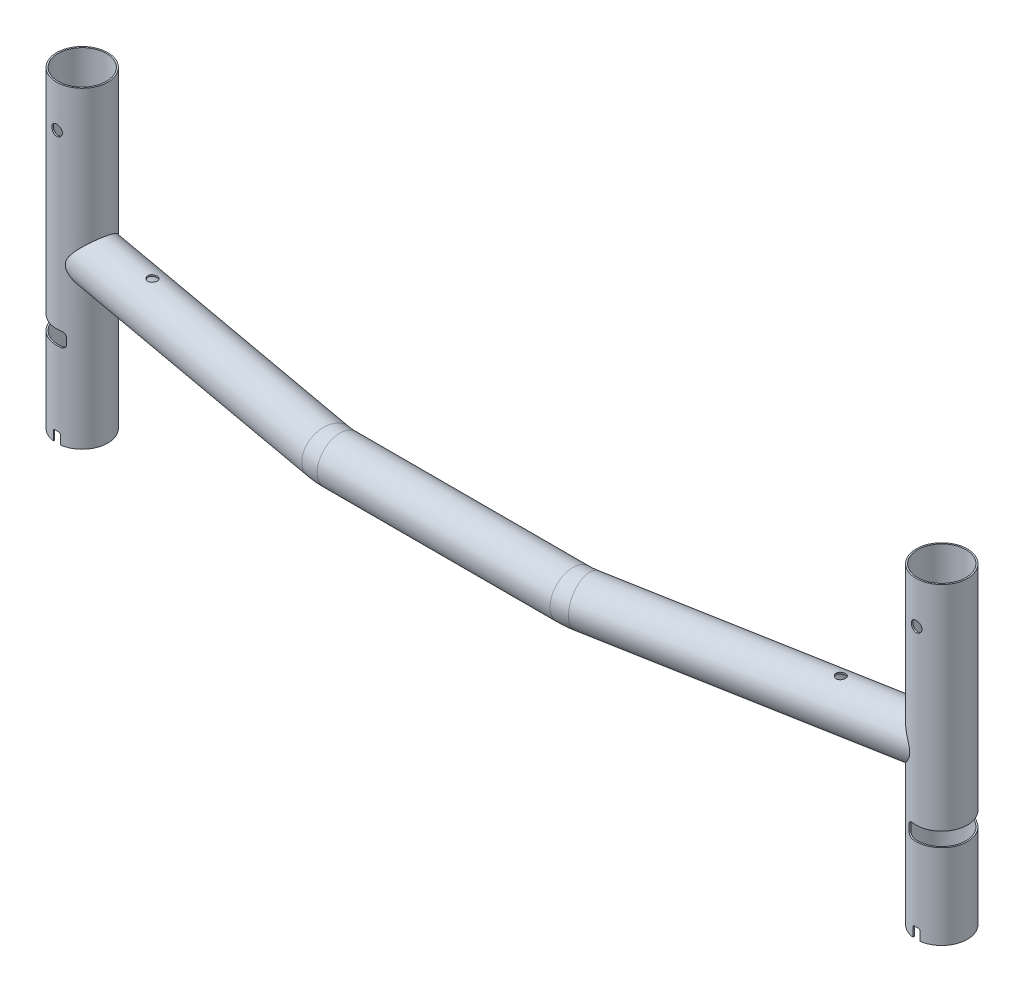
SolidWorks part; units mm, degrees
ref_plane "Front Plane" through (0, 0, 0) normal (0, 0, 1) x (1, 0, 0)
ref_plane "Top Plane" through (0, 0, 0) normal (0, 1, 0) x (1, 0, 0)
ref_plane "Right Plane" through (0, 0, 0) normal (1, 0, 0) x (0, 0, -1)
sketch "Sketch1" plane through (0, 0, 0) normal (0, 1, 0) x (1, 0, 0)
  line L0 (0, 0) -> (0, 107.988) construction
  line L1 (-65, 0) -> (65, 0)
  line L2 (72.1386, 0.6421) -> (234, 30)
  line L3 (-72.1386, 0.6421) -> (-234, 30)
  arc A0 (72.1386, 0.6421) -> (65, 0) centre (65, 40) cw
  arc A1 (-72.1386, 0.6421) -> (-65, 0) centre (-65, 40) ccw
  dimension "D2" = 40
  dimension "D1" = 234
  dimension "D3" = 65
  dimension "D4" = 30
ref_plane "Plane1" through (234, 0, -30) normal (0.9839, 0, -0.1785) x (-0.1785, 0, -0.9839)
sketch "Sketch2" plane through (234, 0, -30) normal (0.9839, 0, -0.1785) x (-0.1785, 0, -0.9839)
  line L0 (0.6421, 0) -> (0, 0) construction
  circle A0 centre (0, 0) radius 12.7
  circle A1 centre (0, 0) radius 11.9
  dimension "D1" = 0.8
  dimension "D2" = 25.4
sweep "Sweep1" add profiles "Sketch2" path "Sketch1"
sketch "Sketch3" plane through (0, 0, 0) normal (0, 1, 0) x (1, 0, 0)
  line L0 (231.7335, 42.4961) -> (236.2665, 17.5039) construction
  line L1 (231.7335, 42.4961) -> (234, 30) construction
  line L2 (234, 30) -> (239.9037, 31.0708) construction
  circle A0 centre (239.9037, 31.0708) radius 14.3
  circle A1 centre (239.9037, 31.0708) radius 13.5
  dimension "D1" = 0.8
  dimension "D3" = 28.6
  dimension "D4" = 0.8
  dimension "D2" = 6
extrude "Boss-Extrude1" add sketch "Sketch3" along normal blind 86.5 and the other way blind 88
sketch "Sketch4" plane through (0, -88, 0) normal (0, -1, 0) x (1, 0, 0)
  circle A0 centre (239.9037, -31.0708) radius 13.5
  dimension "D1" = 27
extrude "Cut-Extrude1" cut sketch "Sketch4" against normal through all
sketch "Sketch5" plane through (234, 0, -30) normal (0.9839, 0, -0.1785) x (-0.1785, 0, -0.9839)
  circle A0 centre (-0.0149, 0) radius 11.9
  dimension "D1" = 23.8
extrude "Cut-Extrude2" cut sketch "Sketch5" against normal blind 88
sketch "Sketch6" plane through (0, 86.5, 0) normal (0, 1, 0) x (1, 0, 0)
  line L0 (239.9037, 31.0708) -> (72.1386, 0.6421)
  line L1 (69.8721, 13.1383) -> (74.4051, -11.854) construction
  line L2 (239.9037, 31.0708) -> (244.4588, 43.7791)
  circle A0 centre (239.9037, 31.0708) radius 13.5 construction
  dimension "D1" = 60
ref_plane "Plane2" through (239.9037, 86.5, -31.0708) normal (0.3374, 0, -0.9414) x (-0.9414, 0, -0.3374)
sketch "Sketch7" plane through (239.9037, 86.5, -31.0708) normal (0.3374, 0, -0.9414) x (-0.9414, 0, -0.3374)
  line L0 (0, -174.5) -> (0, -125.7306) construction
  line L1 (-14.3, -174.5) -> (14.3, -174.5) construction
  line L2 (-12.7, -119.2306) -> (-27.4942, -119.2306)
  line L3 (-27.4942, -119.2306) -> (-27.4942, -127.2306)
  line L4 (-2.5, -119.2306) -> (-12.7, -119.2306)
  line L5 (-2.5, -127.2306) -> (-12.7, -127.2306)
  line L7 (0, -121.7306) -> (0, -124.7306)
  line L8 (-27.4942, -127.2306) -> (-12.7, -127.2306)
  arc A0 (0, -121.7306) -> (-2.5, -119.2306) centre (-2.5, -121.7306) ccw
  arc A1 (0, -124.7306) -> (-2.5, -127.2306) centre (-2.5, -124.7306) cw
  point P12 (0, -123.2306)
  dimension "D1" = 2.5
  dimension "D2" = 51.2694
extrude "Cut-Extrude3" cut sketch "Sketch7" against normal blind 20 and the other way blind 20
sketch "Sketch9" plane through (0, 0, 0) normal (0, 0, 1) x (1, 0, 0)
  line L0 (225.6037, -88) -> (254.2037, -88) construction
  line L1 (238.9037, -82) -> (240.9037, -82)
  line L2 (237.9037, -83) -> (237.9037, -94)
  line L3 (237.9037, -94) -> (241.9037, -94)
  line L4 (241.9037, -83) -> (241.9037, -94)
  line L5 (237.9037, -82) -> (241.9037, -94) construction
  line L6 (237.9037, -94) -> (241.9037, -82) construction
  arc A0 (241.9037, -83) -> (240.9037, -82) centre (240.9037, -83) ccw
  arc A1 (238.9037, -82) -> (237.9037, -83) centre (238.9037, -83) ccw
  point P0 (239.9037, -88)
  dimension "D3" = 1
  dimension "D1" = 12
  dimension "D2" = 4
extrude "Cut-Extrude5" cut sketch "Sketch9" against normal up to surface (17.7198 mm away) up to face at (239.9037, -88, -17.5708)
mirror "Mirror1" about plane through (0, 0, 0) normal (1, 0, 0) of "Cut-Extrude5", "Cut-Extrude2", "Cut-Extrude3", "Boss-Extrude1", "Cut-Extrude1"
sketch "Sketch8" plane through (0, 0, 0) normal (0, 1, 0) x (1, 0, 0)
  line L0 (72.1386, 0.6421) -> (216.9875, 26.5937) construction
  line L1 (69.8721, 13.1383) -> (74.4051, -11.854) construction
  circle A0 centre (216.9875, 26.5937) radius 3
extrude "Cut-Extrude4" cut sketch "Sketch8" against normal up to next
sketch "Sketch10" plane through (0, 0, 0) normal (0, 0, 1) x (1, 0, 0)
  line L0 (0, 0) -> (0, 80.0817) construction
  line L1 (-239.9037, -40.8) -> (-239.9037, 63.2694) construction
  line L3 (-238.8313, -32.7306) -> (-238.8313, -40.7306) construction
  line L4 (-253.4037, -32.7306) -> (-237.7807, -32.7306) construction
  line L5 (-237.7807, -40.7306) -> (-253.4037, -40.7306) construction
  circle A0 centre (-239.9037, 63.2694) radius 2.95
  point P5 (-238.8313, -36.7306)
  dimension "D1" = 100
  dimension "D2" = 5.9
extrude "Cut-Extrude6" cut sketch "Sketch10" against normal through all and the other way through all
sketch "Sketch11" plane through (0, 0, 0) normal (0, 1, 0) x (1, 0, 0)
  line L0 (239.9037, 31.0708) -> (65, 0) construction
  line L1 (65, 12.7) -> (65, -12.7) construction
  line L2 (65, 0) -> (-65, 0) construction
  line L3 (-65, 12.7) -> (-65, -12.7) construction
  line L4 (-65, 0) -> (-239.9037, 31.0708) construction
  line L5 (0, 0) -> (0, 65.6963) construction
  circle A0 centre (192.0842, 22.5759) radius 2.6
  circle A1 centre (-192.0842, 22.5759) radius 2.6
extrude "Cut-Extrude7" cut sketch "Sketch11" along normal through all and the other way through all
mirror "Mirror2" about plane through (0, 0, 0) normal (1, 0, 0) of "Cut-Extrude6"
